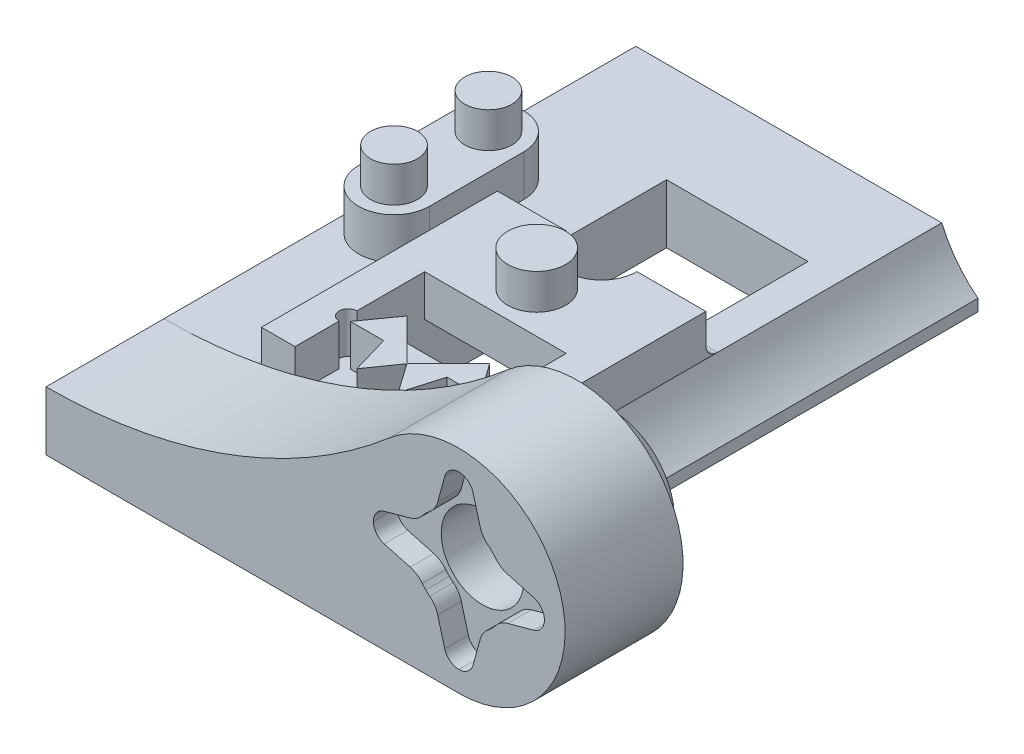
SolidWorks part; units mm, degrees
ref_plane "Front Plane" through (0, 0, 0) normal (0, 0, 1) x (1, 0, 0)
ref_plane "Top Plane" through (0, 0, 0) normal (0, 1, 0) x (1, 0, 0)
ref_plane "Right Plane" through (0, 0, 0) normal (1, 0, 0) x (0, 0, -1)
sketch "Sketch2" plane through (0, 0, 0) normal (0, 0, 1) x (1, 0, 0)
  line L0 (0, -9) -> (-35, -9)
  line L1 (-35, -9) -> (-35, -4)
  circle A0 centre (0, 0) radius 9
  arc A1 (-35, -4) -> (-5.8726, 6.82) centre (-35.0202, 40.6697) ccw
  dimension "D1" = 18
  dimension "D2" = 5
  dimension "D4" = 10.82
  dimension "D3" = 35
extrude "Boss-Extrude1" add sketch "Sketch2" along normal blind 10 contours A1 L1 L0 A0 | A0 region at (-18.5529, -4.8443, 0) region at (0, 0, 0)
sketch "Sketch3" plane through (0, 0, 0) normal (0, 0, -1) x (-1, 0, 0)
  circle A0 centre (0, 0) radius 7
  dimension "D1" = 14
extrude "Boss-Extrude2" add sketch "Sketch3" along normal blind 3 draft 30
sketch "Sketch4" plane through (0, 0, 10) normal (0, 0, 1) x (1, 0, 0)
  line L0 (0, -7.25) -> (0, 7.25) construction
  line L1 (1.2, -6.33) -> (1.8, -4.1378)
  line L2 (0, 0) -> (12.2438, 0) construction
  line L3 (0, 0) -> (8.3889, -8.3889) construction
  line L4 (6.33, -1.2) -> (4.1378, -1.8)
  line L5 (6.33, 1.2) -> (4.1378, 1.8)
  line L6 (1.2, 6.33) -> (1.8, 4.1378)
  line L7 (-1.2, 6.33) -> (-1.8, 4.1378)
  line L8 (-6.33, 1.2) -> (-4.1378, 1.8)
  line L9 (-6.33, -1.2) -> (-4.1378, -1.8)
  line L10 (-1.2, -6.33) -> (-1.8, -4.1378)
  arc A0 (0, -7.25) -> (1.2, -6.33) centre (-0.0057, -6) ccw
  arc A1 (1.8, -4.1378) -> (2.48, -3.1078) centre (3.7276, -4.671) cw
  arc A2 (2.48, -3.1078) -> (2.8116, -2.8116) centre (-0.0153, 0.0185) ccw
  arc A3 (3.1078, -2.48) -> (2.8116, -2.8116) centre (-0.0185, 0.0153) cw
  arc A4 (4.1378, -1.8) -> (3.1078, -2.48) centre (4.671, -3.7276) ccw
  arc A5 (7.25, 0) -> (6.33, -1.2) centre (6, 0.0057) cw
  arc A6 (7.25, 0) -> (6.33, 1.2) centre (6, -0.0057) ccw
  arc A7 (4.1378, 1.8) -> (3.1078, 2.48) centre (4.671, 3.7276) cw
  arc A8 (3.1078, 2.48) -> (2.8116, 2.8116) centre (-0.0185, -0.0153) ccw
  arc A9 (2.48, 3.1078) -> (2.8116, 2.8116) centre (-0.0153, -0.0185) cw
  arc A10 (1.8, 4.1378) -> (2.48, 3.1078) centre (3.7276, 4.671) ccw
  arc A11 (0, 7.25) -> (1.2, 6.33) centre (-0.0057, 6) cw
  arc A12 (0, 7.25) -> (-1.2, 6.33) centre (0.0057, 6) ccw
  arc A13 (-1.8, 4.1378) -> (-2.48, 3.1078) centre (-3.7276, 4.671) cw
  arc A14 (-2.48, 3.1078) -> (-2.8116, 2.8116) centre (0.0153, -0.0185) ccw
  arc A15 (-3.1078, 2.48) -> (-2.8116, 2.8116) centre (0.0185, -0.0153) cw
  arc A16 (-4.1378, 1.8) -> (-3.1078, 2.48) centre (-4.671, 3.7276) ccw
  arc A17 (-7.25, 0) -> (-6.33, 1.2) centre (-6, -0.0057) cw
  arc A18 (-7.25, 0) -> (-6.33, -1.2) centre (-6, 0.0057) ccw
  arc A19 (-4.1378, -1.8) -> (-3.1078, -2.48) centre (-4.671, -3.7276) cw
  arc A20 (-3.1078, -2.48) -> (-2.8116, -2.8116) centre (0.0185, 0.0153) ccw
  arc A21 (-2.48, -3.1078) -> (-2.8116, -2.8116) centre (0.0153, 0.0185) cw
  arc A22 (-1.8, -4.1378) -> (-2.48, -3.1078) centre (-3.7276, -4.671) ccw
  arc A23 (0, -7.25) -> (-1.2, -6.33) centre (0.0057, -6) cw
  point P4 (0, 0)
  point P10 (0, 0)
  dimension "D4" = 1.25
  dimension "D7" = 2
  dimension "D11" = 4
  dimension "D1" = 14.5
  dimension "D2" = 0.92
  dimension "D3" = 1.2
  dimension "D5" = 0.6
  dimension "D6" = 1.03
  dimension "D8" = 0.68
  dimension "D12" = 45
extrude "Cut-Extrude1" cut sketch "Sketch4" against normal blind 2
sketch "Sketch5" plane through (0, 0, 0) normal (0, 0, -1) x (-1, 0, 0)
  line L0 (35, -9) -> (35, -4)
  line L1 (35, -4) -> (9.07, -4)
  line L2 (35, -9) -> (6, -9)
  line L3 (0, -9) -> (35, -9) construction
  line L4 (6, -9) -> (6, -8)
  arc A0 (6, -8) -> (9.07, -4) centre (-0.1416, -0.1082) ccw
  dimension "D4" = 10
  dimension "D1" = 29
  dimension "D2" = 25.93
  dimension "D3" = 1
extrude "Boss-Extrude3" add sketch "Sketch5" along normal blind 40
sketch "Sketch6" plane through (0, -4, 0) normal (0, 1, 0) x (1, 0, 0)
  line L0 (-9.07, 40) -> (-9.07, 0) construction
  line L1 (-11.9, 31.5) -> (-23.9, 31.5)
  line L2 (-11.9, 31.5) -> (-11.9, 8.5)
  line L3 (-11.9, 8.5) -> (-23.9, 8.5)
  line L4 (-23.9, 31.5) -> (-23.9, 8.5)
  line L5 (-35, 40) -> (-9.07, 40) construction
  dimension "D1" = 12
  dimension "D2" = 23
  dimension "D3" = 2.83
  dimension "D4" = 8.5
extrude "Cut-Extrude3" cut sketch "Sketch6" against normal through all
sketch "Sketch7" plane through (0, -4, 0) normal (0, 1, 0) x (1, 0, 0)
  line L0 (-11.9, 20) -> (-51.1, 20) construction
  line L1 (-11.9, 8.5) -> (-11.9, 31.5) construction
  line L2 (-31.5, 16) -> (-31.5, 24) construction
  line L3 (-34.5, 16) -> (-34.5, 24)
  line L4 (-28.5, 16) -> (-28.5, 24)
  line L5 (-35, 40) -> (-35, 0) construction
  arc A0 (-34.5, 16) -> (-28.5, 16) centre (-31.5, 16) ccw
  arc A1 (-28.5, 24) -> (-34.5, 24) centre (-31.5, 24) ccw
  point P6 (-31.5, 20)
  dimension "D2" = 3
  dimension "D1" = 0.5
  dimension "D3" = 8
extrude "Boss-Extrude4" add sketch "Sketch7" along normal blind 3.5
sketch "Sketch8" plane through (0, -0.5, 0) normal (0, 1, 0) x (1, 0, 0)
  line L0 (-34.5, 20) -> (-28.5, 20) construction
  line L1 (-34.5, 24) -> (-34.5, 16) construction
  line L2 (-28.5, 16) -> (-28.5, 24) construction
  line L3 (-31.5, 20) -> (-31.5, 24) construction
  circle A0 centre (-31.5, 24) radius 2
  circle A1 centre (-31.5, 16) radius 2
  dimension "D2" = 4
  dimension "D1" = 4
extrude "Boss-Extrude5" add sketch "Sketch8" along normal blind 3
sketch "Sketch9" plane through (0, 0, -3) normal (0, 0, -1) x (-1, 0, 0)
  circle A0 centre (0, 0) radius 3.5
  dimension "D1" = 7
extrude "Cut-Extrude4" cut sketch "Sketch9" against normal through all
sketch "Sketch10" plane through (0, -4, 0) normal (0, 1, 0) x (1, 0, 0)
  line L0 (-26.74, 0) -> (-26.74, 20)
  line L1 (-35, 0) -> (-9.07, 0) construction
  line L2 (-26.74, 20) -> (-20.91, 20)
  line L3 (-14.91, 20) -> (-9.07, 20)
  line L4 (-9.07, 40) -> (-9.07, 0) construction
  line L5 (-20.91, 20) -> (-14.91, 20) construction
  line L6 (-9.07, 20) -> (-9.07, 0)
  line L7 (-23.9, 3.75) -> (-23.9, 0)
  line L8 (-23.9, 31.5) -> (-23.9, 8.5) construction
  line L9 (-23.9, 3.75) -> (-23.9, 5.25) construction
  line L10 (-23.9, 5.25) -> (-23.9, 11)
  line L11 (-23.9, 11) -> (-11.9, 11)
  line L12 (-17.9, 8.5) -> (-17.9, 13.5) construction
  line L13 (-23.9, 8.5) -> (-11.9, 8.5) construction
  line L14 (-11.9, 3.75) -> (-11.9, 0)
  line L15 (-11.9, 5.25) -> (-11.9, 11)
  line L16 (-26.74, 0) -> (-23.9, 0)
  line L17 (-11.9, 0) -> (-9.07, 0)
  arc A0 (-20.91, 20) -> (-14.91, 20) centre (-17.91, 20) ccw
  arc A1 (-23.9, 5.25) -> (-23.9, 3.75) centre (-23.9, 4.5) ccw
  arc A2 (-11.9, 5.25) -> (-11.9, 3.75) centre (-11.9, 4.5) cw
  point P29 (-17.9, 11)
  dimension "D4" = 6
  dimension "D7" = 0.75
  dimension "D1" = 20
  dimension "D2" = 17.67
  dimension "D3" = 5.83
  dimension "D5" = 3.75
  dimension "D6" = 11
extrude "Boss-Extrude6" add sketch "Sketch10" along normal blind 3.5
sketch "Sketch11" plane through (0, -0.5, 0) normal (0, 1, 0) x (1, 0, 0)
  line L0 (-17.91, 17) -> (-17.9, 11) construction
  line L1 (-23.9, 11) -> (-11.9, 11) construction
  arc A0 (-20.91, 20) -> (-14.91, 20) centre (-17.91, 20) ccw construction
  circle A1 centre (-17.9058, 14.5) radius 2.45
  dimension "D1" = 4.9
  dimension "D2" = 2.5
extrude "Boss-Extrude7" add sketch "Sketch11" along normal blind 3
sketch "Sketch12" plane through (0, -4, 0) normal (0, 1, 0) x (1, 0, 0)
  line L0 (-26.74, 4.2) -> (-9.07, 4.2) construction
  line L1 (-20.58, 4.2) -> (-19.65, 1)
  line L2 (-19.65, 1) -> (-17.93, 3.45)
  line L3 (-26.74, 20) -> (-26.74, 0) construction
  line L4 (-9.07, 0) -> (-9.07, 20) construction
  line L5 (-5.8726, 0) -> (-23.9, 0) construction
  line L6 (-17.9, 8.5) -> (-17.9, 0) construction
  line L7 (-23.9, 8.5) -> (-11.9, 8.5) construction
  line L8 (-23.9, 0) -> (-11.9, 0) construction
  line L9 (-20.58, 4.2) -> (-23.4, 4.2)
  line L10 (-23.4, 4.2) -> (-21.4, 7)
  line L11 (-17.93, 3.45) -> (-17.87, 3.45)
  line L12 (-21.4, 7) -> (-17.95, 3.55)
  line L13 (-17.95, 3.55) -> (-17.85, 3.55)
  line L14 (-14.4, 7) -> (-17.85, 3.55)
  line L15 (-12.4, 4.2) -> (-14.4, 7)
  line L16 (-15.22, 4.2) -> (-12.4, 4.2)
  line L17 (-16.15, 1) -> (-17.87, 3.45)
  line L18 (-15.22, 4.2) -> (-16.15, 1)
  point P23 (-17.9, 3.55)
  point P25 (-17.9, 3.45)
  dimension "D1" = 4.2
  dimension "D2" = 2.82
  dimension "D3" = 2
  dimension "D4" = 3.5
  dimension "D5" = 0.93
  dimension "D6" = 1.72
  dimension "D7" = 0.03
  dimension "D8" = 0.1
  dimension "D9" = 0.05
  dimension "D10" = 3.45
  dimension "D11" = 3.2
  dimension "D12" = 2.8
extrude "Boss-Extrude9" add sketch "Sketch12" along normal blind 3.5
fillet "Fillet1" radius 1 3 edges at (-10.485, -4, -20) (-25.32, -4, -20) (-26.74, -4, -10)
